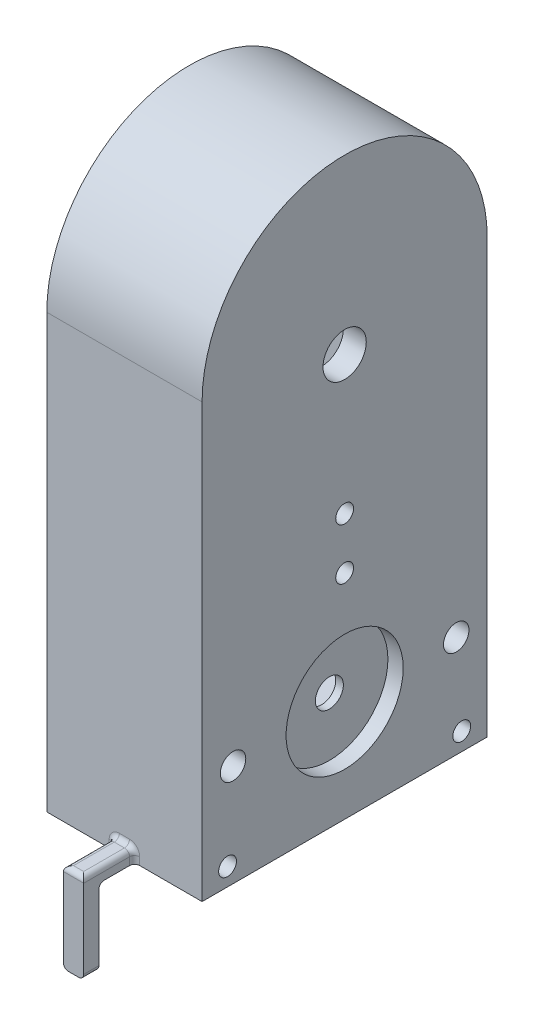
SolidWorks part; units mm, degrees
ref_plane "Front Plane" through (0, 0, 0) normal (0, 0, 1) x (1, 0, 0)
ref_plane "Top Plane" through (0, 0, 0) normal (0, 1, 0) x (1, 0, 0)
ref_plane "Right Plane" through (0, 0, 0) normal (1, 0, 0) x (0, 0, -1)
sketch "Sketch2" plane through (0, 0, 0) normal (0, 1, 0) x (1, 0, 0)
  line L1 (0, 0) -> (30.5, 0)
  line L2 (0, 0) -> (0, -56)
  line L3 (0, -56) -> (30.5, -56)
  line L4 (30.5, 0) -> (30.5, -56)
  circle A0 centre (12.5, -28) radius 4.25
  circle A1 centre (12.5, -28) radius 12
  circle A2 centre (20.9853, -19.5147) radius 2.25
  circle A3 centre (4.0147, -36.4853) radius 2.25
  circle A4 centre (20.9853, -36.4853) radius 2.25
  circle A5 centre (4.0147, -19.5147) radius 2.25
  arc A6 (30.5, 0) -> (0, 0) centre (15.25, 0) ccw
  dimension "D5" = 8.4853
  dimension "D6" = 24
  dimension "D7" = 8.4853
  dimension "D8" = 8.4853
  dimension "D9" = 8.4853
  dimension "D3" = 12.5
  dimension "D1" = 30.5
  dimension "D2" = 56
  dimension "D4" = 28
extrude "Boss-Extrude3" add sketch "Sketch2" along normal blind 85 contours A0 | A1 A5 | A1 A5 | A1 A2 | A1 A2 | A1 A4 | A1 A4 | A1 A3 | A1 A3 | A5 A1 A3 A4 A2 A0 | L4 L1 L2 L3 A5 A1 A2 A4 A3 region at (15.25, 0, 0.6377) region at (12.5, 0, 28) region at (23.6439, 0, 31.4327) region at (20.2839, 0, 20.2161) region at (21.6329, 0, 18.8671) region at (21.6329, 0, 37.1329) region at (20.2839, 0, 35.7839) region at (4.7161, 0, 20.2161) region at (3.3671, 0, 18.8671) region at (3.3671, 0, 37.1329) region at (4.7161, 0, 35.7839)
extrude "Cut-Extrude1" cut sketch "Sketch2<5>" along normal blind 31.75 contours A1 A3 | A1 A3 | A1 A5 | A1 A5 | A1 A4 | A1 A4 | A1 A2 | A1 A2 | A0 region at (12.5, 0, 28) region at (20.2839, 0, 20.2161) region at (21.6329, 0, 18.8671) region at (21.6329, 0, 37.1329) region at (20.2839, 0, 35.7839) region at (4.7161, 0, 20.2161) region at (3.3671, 0, 18.8671) region at (3.3671, 0, 37.1329) region at (4.7161, 0, 35.7839)
sketch "Sketch2<5>" plane through (0, 0, 0) normal (0, 1, 0) x (1, 0, 0) same geometry as "Sketch2"
sketch "Sketch4" plane through (30.5, 0, 0) normal (1, 0, 0) x (0, 0, -1)
  line L0 (0, 85) -> (-56, 85) construction
  line L1 (-56, 85) -> (0, 85)
  arc A0 (0, 85) -> (-56, 85) centre (-28, 85) ccw
extrude "Boss-Extrude4" add sketch "Sketch4" against normal blind 30.5
sketch "Sketch3" plane through (0, 0, 0) normal (-1, 0, 0) x (0, 0, 1)
  line L0 (5, 10) -> (5, 80)
  line L11 (5, 80) -> (5, 85)
  line L12 (51, 80) -> (51, 10)
  line L14 (51, 85) -> (51, 80)
  line L17 (5, 10) -> (5, 7)
  line L18 (5, 7) -> (51, 7)
  line L19 (51, 7) -> (51, 10)
  arc A3 (51, 85) -> (5, 85) centre (28, 85) ccw
extrude "Cut-Extrude2" cut sketch "Sketch3" against normal blind 26
sketch "Sketch5" plane through (26, 0, 0) normal (-1, 0, 0) x (0, 0, 1)
  line L0 (0, 0) -> (56, 0) construction
  line L1 (0, 85) -> (0, 0) construction
  circle A0 centre (28, 20) radius 2.75
  circle A1 centre (28, 79.06) radius 4.25
  circle A6 centre (28, 52) radius 1.75
  dimension "D1" = 52
  dimension "D2" = 59.06
  dimension "D3" = 28
  dimension "D4" = 79.06
extrude "Cut-Extrude3" cut sketch "Sketch5" against normal blind 10
sketch "Sketch6" plane through (30.5, 0, 0) normal (1, 0, 0) x (0, 0, -1)
  line L0 (-28, 20) -> (-49.92, 20)
  line L1 (-28, 20) -> (-6.08, 20)
  line L2 (-28, 20) -> (-28, 41.92)
  circle A14 centre (-49.92, 20) radius 2.5
  circle A15 centre (-6.08, 20) radius 2.5
  circle A16 centre (-28, 41.92) radius 1.75
  circle A17 centre (-28, 20) radius 11
sketch "Sketch7" plane through (30.5, 0, 0) normal (1, 0, 0) x (0, 0, -1)
  circle A0 centre (-28, 20) radius 11.5
extrude "Cut-Extrude5" cut sketch "Sketch7" against normal blind 3
sketch "Sketch9" plane through (0, 0, 0) normal (-1, 0, 0) x (0, 0, 1)
  line L0 (0, 0) -> (56, 0) construction
  circle A0 centre (5, 3.5) radius 1.75
  circle A1 centre (51, 3.5) radius 1.75
  dimension "D1" = 3.5
  dimension "D2" = 3.5
extrude "Cut-Extrude7" cut sketch "Sketch9" against normal blind 77
extrude "Cut-Extrude8" cut sketch "Sketch6" against normal blind 77 contours A15 | A16 | A14
sketch "Sketch11" plane through (0, 0, 56) normal (0, 0, 1) x (1, 0, 0)
  line L1 (0, 0) -> (30.5, 0) construction
  line L2 (15.25, 2.5) -> (17.25, 2.5)
  line L3 (17.25, 2.5) -> (17.25, 0)
  line L4 (17.25, 0) -> (15.25, 0)
  line L5 (15.25, 0) -> (13.25, 0)
  line L6 (13.25, 0) -> (13.25, 2.5)
  line L7 (13.25, 2.5) -> (15.25, 2.5)
extrude "Boss-Extrude5" add sketch "Sketch11" along normal blind 10
sketch "Sketch12" plane through (0, 0, 0) normal (0, -1, 0) x (1, 0, 0)
  line L0 (17.25, 66) -> (17.25, 56) construction
  line L1 (13.25, 66) -> (17.25, 66)
  line L2 (13.25, 66) -> (13.25, 63)
  line L3 (13.25, 63) -> (17.25, 63)
  line L4 (17.25, 66) -> (17.25, 63)
  dimension "D1" = 3
extrude "Boss-Extrude6" add sketch "Sketch12" along normal blind 15
fillet "Fillet2" radius 1 9 edges at (17.25, -15, 64.5) (13.25, -15, 64.5) (15.25, 2.5, 66) (17.25, 1.25, 56) (13.25, 1.25, 56) (15.25, 2.5, 56) (15.25, 0, 63) (17.25, 2.5, 61) (13.25, 2.5, 61)
